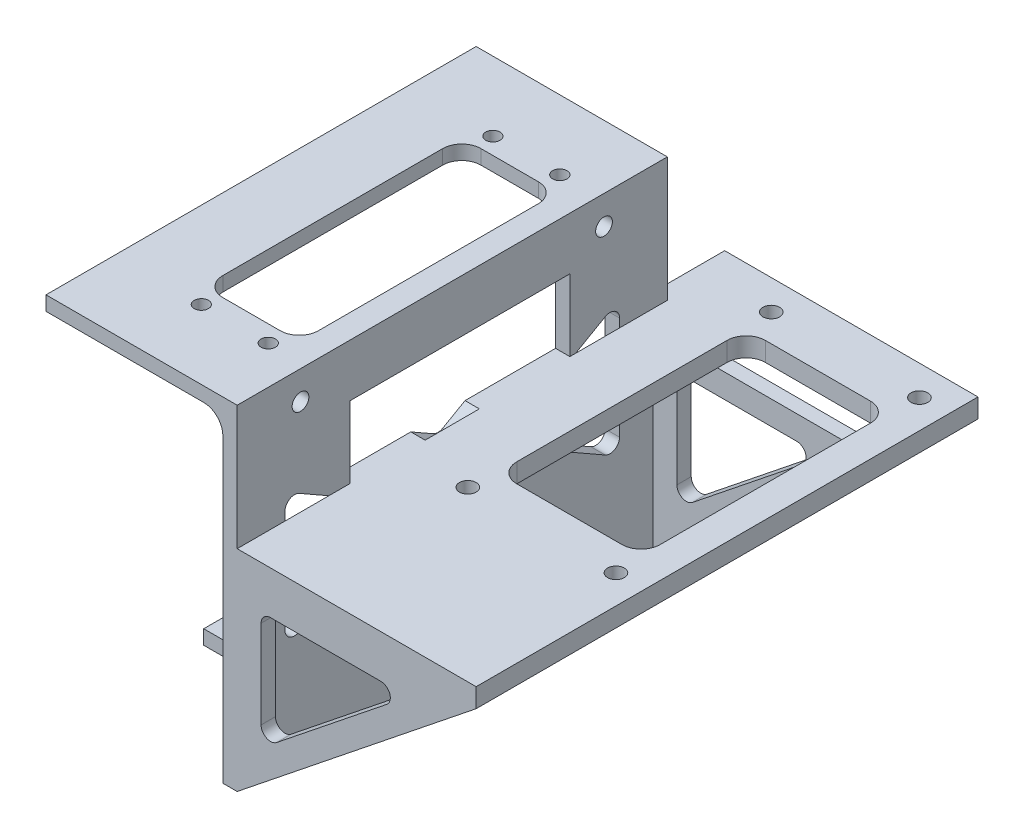
SolidWorks part; units mm, degrees
material "PLA"
ref_plane "前视基准面" through (0, 0, 0) normal (0, 0, 1) x (1, 0, 0)
ref_plane "上视基准面" through (0, 0, 0) normal (0, 1, 0) x (1, 0, 0)
ref_plane "右视基准面" through (0, 0, 0) normal (1, 0, 0) x (0, 0, -1)
sketch "草图1" plane through (0, 0, 0) normal (0, 0, 1) x (1, 0, 0)
  line L1 (-15, -35) -> (15, -35)
  line L2 (-15, -35) -> (-15, 35)
  line L3 (-15, 35) -> (15, 35)
  line L4 (15, -35) -> (15, 35)
  line L5 (-15, -35) -> (15, 35) construction
  line L6 (-15, 35) -> (15, -35) construction
  point P0 (0, 0)
  dimension "D1" = 70
  dimension "D2" = 30
extrude "凸台-拉伸1" add sketch "草图1" along normal blind 90
sketch "草图2" plane through (0, 0, 0) normal (0, 0, -1) x (-1, 0, 0)
  line L6 (15, -32) -> (-12, -32)
  line L7 (-12, -32) -> (-12, 32)
  line L8 (-12, 32) -> (15, 32)
  line L9 (15, 32) -> (15, -32)
extrude "切除-拉伸1" cut sketch "草图2" against normal blind 108
sketch "草图3" plane through (15, 0, 0) normal (1, 0, 0) x (0, 0, -1)
  circle A4 centre (-13.25, -2) radius 1.75
  circle A5 centre (-13.25, 29) radius 1.75
  circle A6 centre (-76.75, -2) radius 1.75
  circle A7 centre (-76.75, 29) radius 1.75
extrude "切除-拉伸2" cut sketch "草图3" against normal blind 14.3
sketch "草图5" plane through (0, 35, 0) normal (0, 1, 0) x (1, 0, 0)
  circle A4 centre (-9, -14.2) radius 1.25
  circle A5 centre (5.7, -24.85) radius 1.25
  circle A6 centre (5.7, -75.8) radius 1.3
  circle A7 centre (-9, -75.8) radius 1.25
extrude "切除-拉伸3" [suppressed] cut sketch "草图5" against normal blind 14.3
sketch "草图6" plane through (0, -32, 0) normal (0, 1, 0) x (1, 0, 0)
  circle A2 centre (0, -30) radius 1.5
  circle A3 centre (0, -60) radius 1.5
extrude "切除-拉伸4" cut sketch "草图6" against normal blind 14.3
sketch "草图7" plane through (0, -32, 0) normal (0, 1, 0) x (1, 0, 0)
  line L2 (10, -67) -> (-15, -67)
  line L3 (-15, -23) -> (10, -23)
  line L4 (15, 0) -> (-15, 0) construction
  line L5 (-15, -23) -> (12, -23)
  line L6 (-15, -23) -> (-15, 0)
  line L7 (-15, 0) -> (12, 0)
  line L8 (12, -23) -> (12, 0)
  line L9 (15, -90) -> (-15, -90) construction
  line L10 (-15, -67) -> (12, -67)
  line L11 (-15, -67) -> (-15, -90)
  line L12 (-15, -90) -> (12, -90)
  line L13 (12, -67) -> (12, -90)
  line M3 (12, -90) -> (12, 0)
  line M4 (12, 0) -> (-15, 0)
  line M5 (-15, 0) -> (-15, -90)
  line M6 (-15, -90) -> (12, -90)
  dimension "D1" = 23
  dimension "D2" = 27
  dimension "D3" = 23
  dimension "D4" = 27
extrude "切除-拉伸5" cut sketch "草图7" against normal blind 10 contours L10 L2 M5 M6 M3 | L3 L5 M3 M4 M5 region at (-1.5, -32, 78.5) region at (-1.5, -32, 11.5)
sketch "草图8" plane through (0, -35, 0) normal (0, -1, 0) x (1, 0, 0)
  line L0 (-1.5, 23) -> (12, 0)
  line L1 (-15, 23) -> (12, 23) construction
  line L2 (12, 0) -> (12, 23)
  line L3 (12, 23) -> (-1.5, 23)
  line L4 (-15, 45) -> (22.827, 45) construction
  line L5 (-15, 67) -> (-15, 23) construction
  line L6 (12, 67) -> (-1.5, 67)
  line L7 (12, 90) -> (12, 67)
  line L8 (-1.5, 67) -> (12, 90)
extrude "凸台-拉伸2" add sketch "草图8" against normal blind 3
fillet "圆角1" radius 10 2 edges at (-1.5, -33.5, 23) (-1.5, -33.5, 67)
fillet "圆角2" radius 4 1 edges at (12, -32, 45)
fillet "圆角3" radius 4 1 edges at (12, 32, 45)
sketch "草图14" plane through (-15, 0, 0) normal (-1, 0, 0) x (0, 0, 1)
  line L4 (0, 35) -> (0, 32)
  line L5 (0, 32) -> (90, 32)
  line L6 (90, 32) -> (90, 35)
  line L7 (90, 35) -> (0, 35)
  line L8 (0, 35) -> (0, 32)
  line L9 (0, 32) -> (90, 32)
  line L10 (90, 32) -> (90, 35)
  line L11 (90, 35) -> (0, 35)
  dimension "D1" = 0
extrude "凸台-拉伸4" add sketch "草图14" along normal blind 10
sketch "草图11" plane through (0, 35, 0) normal (0, 1, 0) x (1, 0, 0)
  line L0 (-13, -45) -> (0, -45) construction
  line L3 (-7, -75.5) -> (7, -75.5) construction
  line L4 (-7, -75.5) -> (-7, -14.5) construction
  line L5 (-7, -14.5) -> (7, -14.5) construction
  line L6 (7, -75.5) -> (7, -14.5) construction
  line L7 (-7, -75.5) -> (7, -14.5) construction
  line L8 (-7, -14.5) -> (7, -75.5) construction
  line L9 (-10, -72) -> (10, -72)
  line L10 (-10, -72) -> (-10, -18)
  line L11 (-10, -18) -> (10, -18)
  line L12 (10, -72) -> (10, -18)
  line L13 (-10, -72) -> (10, -18) construction
  line L14 (-10, -18) -> (10, -72) construction
  circle A0 centre (-7, -14.5) radius 1.5
  circle A1 centre (7, -14.5) radius 1.5
  circle A2 centre (-7, -75.5) radius 1.5
  circle A3 centre (7, -75.5) radius 1.5
  dimension "D4" = 3
  dimension "D5" = 3
  dimension "D6" = 3
  dimension "D7" = 3
  dimension "D1" = 13
  dimension "D2" = 61
  dimension "D3" = 14
  dimension "D8" = 54
  dimension "D9" = 20
extrude "切除-拉伸8" cut sketch "草图11" against normal blind 10
fillet "圆角5" radius 4 4 edges at (-10, 33.5, 72) (10, 33.2321, 72) (10, 33.2321, 18) (-10, 33.5, 18)
sketch "草图12" plane through (15, 0, 0) normal (1, 0, 0) x (0, 0, -1)
  line L0 (-45, 35) -> (-45, -35) construction
  line L1 (-90, 35) -> (0, 35) construction
  line L2 (-90, -35) -> (0, -35) construction
  line L3 (-82.4807, 15.6588) -> (-12.4807, -24.3412)
  line L4 (-80, -20) -> (-10, -20)
  line L5 (-80, -20) -> (-80, 20)
  line L6 (-80, 20) -> (-10, 20)
  line L7 (-10, -20) -> (-10, 20)
  line L8 (-80, -20) -> (-10, 20) construction
  line L9 (-80, 20) -> (-10, -20) construction
  line L10 (-77.5193, -24.3412) -> (-7.5193, 15.6588)
  line L11 (-77.5193, 24.3412) -> (-7.5193, -15.6588)
  line L12 (-82.4807, -15.6588) -> (-12.4807, 24.3412)
  point P6 (-45, 0)
  dimension "D1" = 40
  dimension "D2" = 70
  dimension "D3" = 5
  dimension "D4" = 5
extrude "切除-拉伸9" cut sketch "草图12" against normal blind 10 contours L11 L12 L6 | L10 L11 L7 L3 | L5 L12 L3 L1 | L10 L4 L3 region at (15, 0, 71.6926) region at (15, -15.2529, 45) region at (15, 15.2529, 45) region at (15, 0, 18.3074)
fillet "圆角6" radius 2 12 edges at (13.5, -14.2412, 10) (13.5, 0, 34.9222) (13.5, -5.7588, 45) (13.5, -20, 20.0778) (13.5, -20, 69.9222) (13.5, 14.2412, 80) (13.5, 0, 55.0778) (13.5, -14.2412, 80) (13.5, 14.2412, 10) (13.5, 20, 69.9222) (13.5, 20, 20.0778) (13.5, 5.7588, 45)
sketch "草图13" plane through (15, 0, 0) normal (1, 0, 0) x (0, 0, -1)
  line L6 (-90, 35) -> (-90, 5) construction
  line L7 (-90, -35) -> (-90, 35) construction
  line L9 (-90, 5) -> (0, 5)
  line L10 (-90, 5) -> (-90, 9)
  line L11 (-90, 9) -> (0, 9)
  line L12 (0, 5) -> (0, 9)
  line L13 (0, -35) -> (0, 35) construction
  dimension "D1" = 30
  dimension "D2" = 4
  dimension "D3" = 90
extrude "凸台-拉伸7" add sketch "草图13" along normal blind 50
sketch "草图24" plane through (0, 0, 0) normal (0, 0, -1) x (-1, 0, 0)
  line L1 (-65, 9) -> (-12, 9)
  line L2 (-65, 9) -> (-65, 5)
  line L3 (-65, 5) -> (-12, 5)
  line L4 (-12, 9) -> (-12, 5)
  line L5 (-12, 28) -> (-12, -28) construction
  dimension "D1" = 4
  dimension "D2" = 53
extrude "凸台-拉伸10" add sketch "草图24" along normal blind 15
sketch "草图16" plane through (0, 9, 0) normal (0, 1, 0) x (1, 0, 0)
  circle A4 centre (59, 8.75) radius 1.75
  circle A5 centre (28, 8.75) radius 1.75
  circle A6 centre (59, -54.75) radius 1.75
  circle A7 centre (28, -54.75) radius 1.75
extrude "切除-拉伸10" cut sketch "草图16" against normal blind 10
sketch "草图18" plane through (15, 0, 0) normal (1, 0, 0) x (0, 0, -1)
  line L0 (-62.391, 20) -> (-66.391, 20) construction
  line L1 (-66.391, 20) -> (-66.391, 24) construction
  line L3 (-66.391, 24) -> (-20.391, 24)
  line L4 (-66.391, 24) -> (-66.391, 9)
  line L5 (-66.391, 9) -> (-20.391, 9)
  line L6 (-20.391, 24) -> (-20.391, 9)
  line L7 (-19.1722, 9) -> (-39.3278, 9) construction
  dimension "D1" = 4
  dimension "D2" = 4
  dimension "D3" = 15
  dimension "D4" = 46
extrude "切除-拉伸11" cut sketch "草图18" against normal blind 10
sketch "草图19" plane through (0, 0, 0) normal (0, 0, -1) x (-1, 0, 0)
  line L3 (-65, 5) -> (-15, 5)
  line L4 (-15, 5) -> (-15, -35)
  line L5 (-15, -35) -> (-65, 5)
extrude "凸台-拉伸8" add sketch "草图19" against normal blind 3
sketch "草图20" plane through (0, 0, 90) normal (0, 0, 1) x (1, 0, 0)
  line L0 (15, -35) -> (65, 5)
  line L1 (65, 5) -> (15, 5)
  line L2 (15, 5) -> (15, -35)
extrude "凸台-拉伸9" add sketch "草图20" against normal blind 3
sketch "草图21" plane through (0, 0, 0) normal (0, 0, -1) x (-1, 0, 0)
  line L4 (-50.7461, 0) -> (-20, -24.5969)
  line L5 (-20, 0) -> (-20, -24.5969)
  line L6 (-50.7461, 0) -> (-20, 0)
extrude "切除-拉伸12" cut sketch "草图21" against normal blind 108
fillet "圆角7" radius 2 6 edges at (50.7461, 0, 88.5) (20, -24.5969, 88.5) (20, 0, 88.5) (20, 0, 1.5) (20, -24.5969, 1.5) (50.7461, 0, 1.5)
sketch "草图22" plane through (0, 9, 0) normal (0, 1, 0) x (1, 0, 0)
  line L0 (28, -54.75) -> (59, -54.75) construction
  line L1 (59, -54.75) -> (59, 8.75) construction
  line L2 (59, -23) -> (43.5, -23) construction
  line L4 (28.5, -49) -> (58.5, -49)
  line L5 (28.5, -49) -> (28.5, 3)
  line L6 (28.5, 3) -> (58.5, 3)
  line L7 (58.5, -49) -> (58.5, 3)
  line L8 (28.5, -49) -> (58.5, 3) construction
  line L9 (28.5, 3) -> (58.5, -49) construction
  dimension "D1" = 15.5
  dimension "D2" = 52
  dimension "D3" = 30
extrude "切除-拉伸13" cut sketch "草图22" against normal blind 4
fillet "圆角8" radius 4 4 edges at (28.5, 7, 49) (58.5, 7, 49) (58.5, 7, -3) (28.5, 7, -3)
